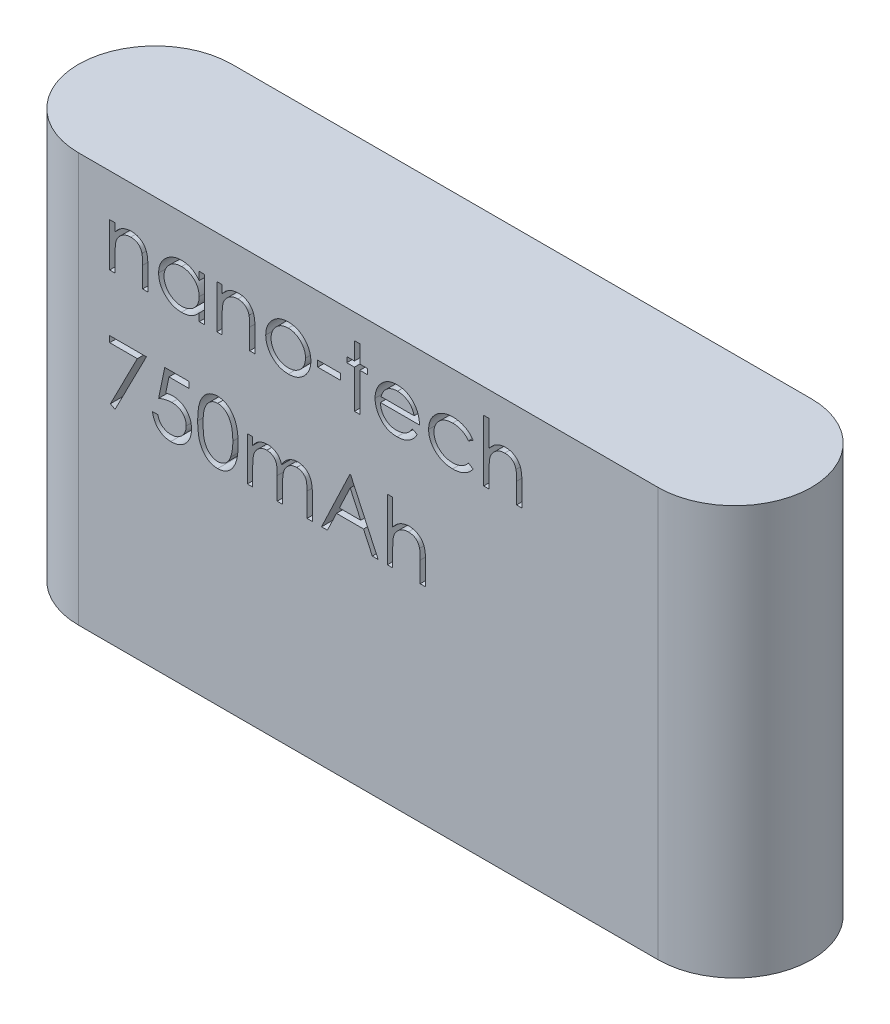
SolidWorks part; units mm, degrees
ref_plane "Přední rovina" through (0, 0, 0) normal (0, 0, 1) x (1, 0, 0)
ref_plane "Horní rovina" through (0, 0, 0) normal (0, 1, 0) x (1, 0, 0)
ref_plane "Pravá rovina" through (0, 0, 0) normal (1, 0, 0) x (0, 0, -1)
sketch "Skica1" plane through (0, 0, 0) normal (0, 0, 1) x (1, 0, 0)
  line L1 (0, 0) -> (-43, 0)
  line L2 (0, 0) -> (0, 24)
  line L3 (0, 24) -> (-43, 24)
  line L4 (-43, 0) -> (-43, 24)
  dimension "D1" = 43
  dimension "D2" = 24
extrude "Přidat vysunutím1" add sketch "Skica1" along normal blind 9
fillet "Zaoblit1" 2 edges at (-43, 12, 9) (-43, 12, 0) type full round first side face at (-21.5, 12, 9) second side face at (-21.5, 12, 0) middle face at (-43, 12, 4.5)
fillet "Zaoblit2" 2 edges at (0, 12, 0) (0, 12, 9) type full round first side face at (-19.25, 12, 0) second side face at (-19.25, 12, 9) middle face at (0, 12, 4.5)
sketch "Skica2" plane through (0, 0, 9) normal (0, 0, 1) x (1, 0, 0)
  text T0 "nano-tech\r\n750mAh"
extrude "Odebrat vysunutím1" cut sketch "Skica2" against normal blind 6
